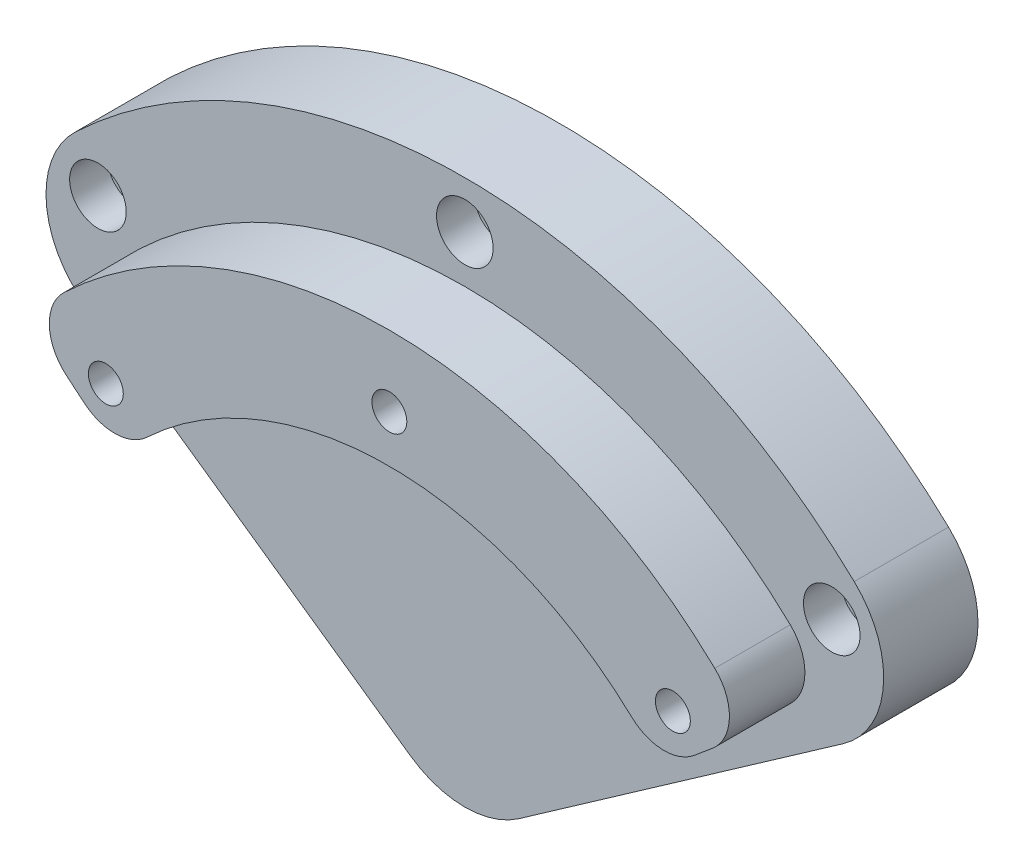
SolidWorks part; units mm, degrees
ref_plane "前视基准面" through (0, 0, 0) normal (0, 0, 1) x (1, 0, 0)
ref_plane "上视基准面" through (0, 0, 0) normal (0, 1, 0) x (1, 0, 0)
ref_plane "右视基准面" through (0, 0, 0) normal (1, 0, 0) x (0, 0, -1)
other "Configuration Table"
sketch "草图1" plane through (0, 0, 0) normal (0, 0, 1) x (1, 0, 0)
  line L0 (0, 60) -> (0, -60) construction
  line L1 (0, 0) -> (-49.1491, 34.4146)
  line L2 (0, 0) -> (49.1491, 34.4146)
  circle A0 centre (0, 0) radius 60
  dimension "D1" = 120
  dimension "D2" = 55
  dimension "D3" = 55
extrude "凸台-拉伸1" add sketch "草图1" along normal blind 10 contours A0 L0 L2 | L0 A0 L1 region at (17.7689, 34.1338, 0) region at (-17.7689, 34.1338, 0)
fillet "圆角1" radius 10 3 edges at (49.1491, 34.4146, 5) (-49.1491, 34.4146, 5) (0, 0, 5)
sketch "草图2" plane through (0, 0, 10) normal (0, 0, 1) x (1, 0, 0)
  line L2 (5.7358, 4.0162) -> (40.1301, 28.0994)
  line L3 (-40.1301, 28.0994) -> (-5.7358, 4.0162)
  line L4 (5.7358, 4.0162) -> (40.1301, 28.0994)
  line L5 (-40.1301, 28.0994) -> (-5.7358, 4.0162)
  circle A0 centre (0, 0) radius 55
  circle A1 centre (0, 55) radius 1.6
  circle A2 centre (38.8909, 38.8909) radius 1.6
  circle A3 centre (55, 0) radius 1.6
  arc A4 (40.1301, 28.0994) -> (41.2732, 43.5491) centre (34.3943, 36.2909) ccw
  arc A5 (41.2732, 43.5491) -> (-41.2732, 43.5491) centre (0, 0) ccw
  arc A6 (-41.2732, 43.5491) -> (-40.1301, 28.0994) centre (-34.3943, 36.2909) ccw
  arc A7 (-5.7358, 4.0162) -> (5.7358, 4.0162) centre (0, 12.2077) ccw
  arc A8 (40.1301, 28.0994) -> (41.2732, 43.5491) centre (34.3943, 36.2909) ccw
  arc A9 (41.2732, 43.5491) -> (-41.2732, 43.5491) centre (0, 0) ccw
  arc A10 (-41.2732, 43.5491) -> (-40.1301, 28.0994) centre (-34.3943, 36.2909) ccw
  arc A11 (-5.7358, 4.0162) -> (5.7358, 4.0162) centre (0, 12.2077) ccw
  circle A12 centre (38.8909, -38.8909) radius 1.6
  circle A13 centre (0, -55) radius 1.6
  circle A14 centre (-38.8909, -38.8909) radius 1.6
  circle A15 centre (-55, 0) radius 1.6
  circle A16 centre (-38.8909, 38.8909) radius 1.6
  point P29 (0, 0)
  dimension "D2" = 110
  dimension "D3" = 3.2
  dimension "D1" = 0
  dimension "D4" = 8
extrude "切除-拉伸1" cut sketch "草图2" against normal blind 10 contours A0 A16 | A0 A16 | A0 A1 | A0 A1 | A0 A2 | A0 A2 region at (38.4078, 38.4078, 10) region at (39.3681, 39.3681, 10) region at (-39.3681, 39.3681, 10) region at (-38.4078, 38.4078, 10) region at (0, 54.3168, 10) region at (0, 55.6749, 10)
sketch "草图3" plane through (0, 0, 10) normal (0, 0, 1) x (1, 0, 0)
  line L0 (0, 0) -> (38.3022, 32.1394)
  line L1 (0, 0) -> (-38.3022, 32.1394)
  line L2 (5.7358, 4.0162) -> (40.1301, 28.0994)
  line L3 (-40.1301, 28.0994) -> (-5.7358, 4.0162)
  line L4 (5.7358, 4.0162) -> (40.1301, 28.0994)
  line L5 (-40.1301, 28.0994) -> (-5.7358, 4.0162)
  line L6 (0, 50) -> (0, 0) construction
  circle A0 centre (0, 0) radius 37.5
  circle A1 centre (0, 0) radius 50
  circle A2 centre (0, 0) radius 42.5
  circle A3 centre (0, 42.5) radius 1.85
  arc A4 (40.1301, 28.0994) -> (41.2732, 43.5491) centre (34.3943, 36.2909) ccw
  arc A5 (41.2732, 43.5491) -> (-41.2732, 43.5491) centre (0, 0) ccw
  arc A6 (-41.2732, 43.5491) -> (-40.1301, 28.0994) centre (-34.3943, 36.2909) ccw
  arc A7 (-5.7358, 4.0162) -> (5.7358, 4.0162) centre (0, 12.2077) ccw
  arc A8 (40.1301, 28.0994) -> (41.2732, 43.5491) centre (34.3943, 36.2909) ccw
  arc A9 (41.2732, 43.5491) -> (-41.2732, 43.5491) centre (0, 0) ccw
  arc A10 (-41.2732, 43.5491) -> (-40.1301, 28.0994) centre (-34.3943, 36.2909) ccw
  arc A11 (-5.7358, 4.0162) -> (5.7358, 4.0162) centre (0, 12.2077) ccw
  circle A12 centre (30.052, 30.052) radius 1.85
  circle A13 centre (42.5, 0) radius 1.85
  circle A14 centre (30.052, -30.052) radius 1.85
  circle A15 centre (0, -42.5) radius 1.85
  circle A16 centre (-30.052, -30.052) radius 1.85
  circle A17 centre (-42.5, 0) radius 1.85
  circle A18 centre (-30.052, 30.052) radius 1.85
  point P32 (0, 0)
  dimension "D2" = 75
  dimension "D3" = 100
  dimension "D4" = 85
  dimension "D5" = 3.7
  dimension "D7" = 50
  dimension "D8" = 50
  dimension "D1" = 0
  dimension "D6" = 8
extrude "凸台-拉伸2" add sketch "草图3" along normal blind 8 contours A3 L6 A0 L0 A2 A12 | A1 L6 A3 A2 A12 L0 | L6 A1 L1 A2 A18 A3 | L6 A3 A2 A18 L1 A0 region at (16.2256, 35.2351, 10) region at (-16.2256, 35.2351, 10) region at (18.9265, 40.8502, 10) region at (-18.9265, 40.8502, 10)
fillet "圆角2" radius 5 4 edges at (-38.3022, 32.1394, 14) (-28.7267, 24.1045, 14) (28.7267, 24.1045, 14) (38.3022, 32.1394, 14)
sketch "草图4" plane through (0, 0, 18) normal (0, 0, 1) x (1, 0, 0)
  line L2 (32.3308, 27.1288) -> (34.2585, 28.7463)
  line L3 (-34.2585, 28.7463) -> (-32.3308, 27.1288)
  line L4 (32.3308, 27.1288) -> (34.2585, 28.7463)
  line L5 (-34.2585, 28.7463) -> (-32.3308, 27.1288)
  circle A0 centre (30.052, 30.052) radius 1.85 construction
  circle A1 centre (0, 42.5) radius 1.85 construction
  circle A2 centre (-30.052, 30.052) radius 1.85 construction
  circle A3 centre (30.052, 30.052) radius 1.85
  circle A4 centre (0, 42.5) radius 1.85
  circle A5 centre (-30.052, 30.052) radius 1.85
  arc A6 (25.6913, 27.3167) -> (-25.6913, 27.3167) centre (0, 0) ccw
  arc A7 (25.6913, 27.3167) -> (32.3308, 27.1288) centre (29.1169, 30.959) ccw
  arc A8 (34.2585, 28.7463) -> (34.494, 36.1962) centre (31.0446, 32.5766) ccw
  arc A9 (34.494, 36.1962) -> (-34.494, 36.1962) centre (0, 0) ccw
  arc A10 (-34.494, 36.1962) -> (-34.2585, 28.7463) centre (-31.0446, 32.5766) ccw
  arc A11 (-32.3308, 27.1288) -> (-25.6913, 27.3167) centre (-29.1169, 30.959) ccw
  arc A12 (25.6913, 27.3167) -> (-25.6913, 27.3167) centre (0, 0) ccw
  arc A13 (25.6913, 27.3167) -> (32.3308, 27.1288) centre (29.1169, 30.959) ccw
  arc A14 (34.2585, 28.7463) -> (34.494, 36.1962) centre (31.0446, 32.5766) ccw
  arc A15 (34.494, 36.1962) -> (-34.494, 36.1962) centre (0, 0) ccw
  arc A16 (-34.494, 36.1962) -> (-34.2585, 28.7463) centre (-31.0446, 32.5766) ccw
  arc A17 (-32.3308, 27.1288) -> (-25.6913, 27.3167) centre (-29.1169, 30.959) ccw
  circle M19 centre (30.052, 30.052) radius 1.85
  circle M20 centre (0, 42.5) radius 1.85
  dimension "D1" = 0
extrude "切除-拉伸2" cut sketch "草图4" against normal through all contours M20 | M19 | A5 region at (30.052, 30.052, 18) region at (0, 42.5, 18)
sketch "草图5" plane through (0, 0, 0) normal (0, 0, -1) x (-1, 0, 0)
  line L2 (-40.1301, 28.0994) -> (-5.7358, 4.0162)
  line L3 (5.7358, 4.0162) -> (40.1301, 28.0994)
  line L4 (-40.1301, 28.0994) -> (-5.7358, 4.0162)
  line L5 (5.7358, 4.0162) -> (40.1301, 28.0994)
  circle A0 centre (-30.052, 30.052) radius 1.85 construction
  circle A1 centre (30.052, 30.052) radius 1.85 construction
  circle A2 centre (0, 42.5) radius 1.85 construction
  circle A3 centre (-30.052, 30.052) radius 1.85
  arc A4 (41.2732, 43.5491) -> (-41.2732, 43.5491) centre (0, 0) ccw
  arc A5 (-41.2732, 43.5491) -> (-40.1301, 28.0994) centre (-34.3943, 36.2909) ccw
  arc A6 (-5.7358, 4.0162) -> (5.7358, 4.0162) centre (0, 12.2077) ccw
  arc A7 (40.1301, 28.0994) -> (41.2732, 43.5491) centre (34.3943, 36.2909) ccw
  arc A8 (41.2732, 43.5491) -> (-41.2732, 43.5491) centre (0, 0) ccw
  arc A9 (-41.2732, 43.5491) -> (-40.1301, 28.0994) centre (-34.3943, 36.2909) ccw
  arc A10 (-5.7358, 4.0162) -> (5.7358, 4.0162) centre (0, 12.2077) ccw
  arc A11 (40.1301, 28.0994) -> (41.2732, 43.5491) centre (34.3943, 36.2909) ccw
  circle A12 centre (30.052, 30.052) radius 1.85
  circle A13 centre (0, 42.5) radius 1.85
  circle A14 centre (-30.052, 30.052) radius 3.25
  circle A15 centre (0, 42.5) radius 3.25
  circle A16 centre (30.052, 30.052) radius 3.25
  circle M17 centre (-30.052, 30.052) radius 1.85
  circle M18 centre (0, 42.5) radius 1.85
  dimension "D2" = 6.5
  dimension "D3" = 6.5
  dimension "D4" = 6.5
  dimension "D1" = 0
extrude "切除-拉伸3" cut sketch "草图5" against normal blind 5 contours A14 M17 | A15 M18 | A12 | A16 region at (33.2101, 30.052, 0) region at (3.1581, 42.5, 0)
sketch "草图7" plane through (0, 0, 10) normal (0, 0, 1) x (1, 0, 0)
  line L2 (-34.2585, 28.7463) -> (-32.3308, 27.1288)
  line L3 (32.3308, 27.1288) -> (34.2585, 28.7463)
  line L4 (-34.2585, 28.7463) -> (-32.3308, 27.1288)
  line L5 (32.3308, 27.1288) -> (34.2585, 28.7463)
  circle A0 centre (-38.8909, 38.8909) radius 3
  circle A1 centre (38.8909, 38.8909) radius 1.6
  circle A2 centre (38.8909, 38.8909) radius 1.6
  circle A3 centre (0, 55) radius 1.6
  circle A4 centre (0, 55) radius 1.6
  circle A5 centre (-38.8909, 38.8909) radius 1.6
  circle A6 centre (-38.8909, 38.8909) radius 1.6
  circle A7 centre (0, 55) radius 3
  circle A8 centre (38.8909, 38.8909) radius 3
  arc A12 (25.6913, 27.3167) -> (-25.6913, 27.3167) centre (0, 0) ccw
  arc A13 (-32.3308, 27.1288) -> (-25.6913, 27.3167) centre (-29.1169, 30.959) ccw
  arc A14 (-34.494, 36.1962) -> (-34.2585, 28.7463) centre (-31.0446, 32.5766) ccw
  arc A15 (34.494, 36.1962) -> (-34.494, 36.1962) centre (0, 0) ccw
  arc A16 (34.2585, 28.7463) -> (34.494, 36.1962) centre (31.0446, 32.5766) ccw
  arc A17 (25.6913, 27.3167) -> (32.3308, 27.1288) centre (29.1169, 30.959) ccw
  arc A18 (25.6913, 27.3167) -> (-25.6913, 27.3167) centre (0, 0) ccw
  arc A19 (-32.3308, 27.1288) -> (-25.6913, 27.3167) centre (-29.1169, 30.959) ccw
  arc A20 (-34.494, 36.1962) -> (-34.2585, 28.7463) centre (-31.0446, 32.5766) ccw
  arc A21 (34.494, 36.1962) -> (-34.494, 36.1962) centre (0, 0) ccw
  arc A22 (34.2585, 28.7463) -> (34.494, 36.1962) centre (31.0446, 32.5766) ccw
  arc A23 (25.6913, 27.3167) -> (32.3308, 27.1288) centre (29.1169, 30.959) ccw
  dimension "D5" = 6
  dimension "D6" = 6
  dimension "D7" = 6
  dimension "D1" = 0
  dimension "D2" = 0
  dimension "D3" = 0
  dimension "D4" = 0
extrude "切除-拉伸5" cut sketch "草图7" against normal blind 4 contours A0 | A7 | A8
move or copy body "实体-移动/复制1" [suppressed] bodies to move or copy 112 parameters "D1"=0, "D2"=0, "D3"=0
move or copy body "实体-移动/复制2" [suppressed] bodies to move or copy 113 parameters "D1"=0, "D2"=0, "D3"=0
move or copy body "实体-移动/复制3" [suppressed] bodies to move or copy 114 parameters "D1"=0, "D2"=0, "D3"=0
move or copy body "实体-移动/复制4" [suppressed] bodies to move or copy 115 parameters "D1"=0, "D2"=0, "D3"=0
move or copy body "实体-移动/复制5" [suppressed] bodies to move or copy 116 parameters "D1"=0, "D2"=0, "D3"=0
move or copy body "实体-移动/复制6" [suppressed] bodies to move or copy 117 parameters "D1"=0, "D2"=0, "D3"=0
move or copy body "实体-移动/复制7" [suppressed] bodies to move or copy 118 parameters "D1"=0, "D2"=0, "D3"=0
move or copy body "实体-移动/复制8" [suppressed] bodies to move or copy 119 parameters "D1"=0, "D2"=0, "D3"=0
